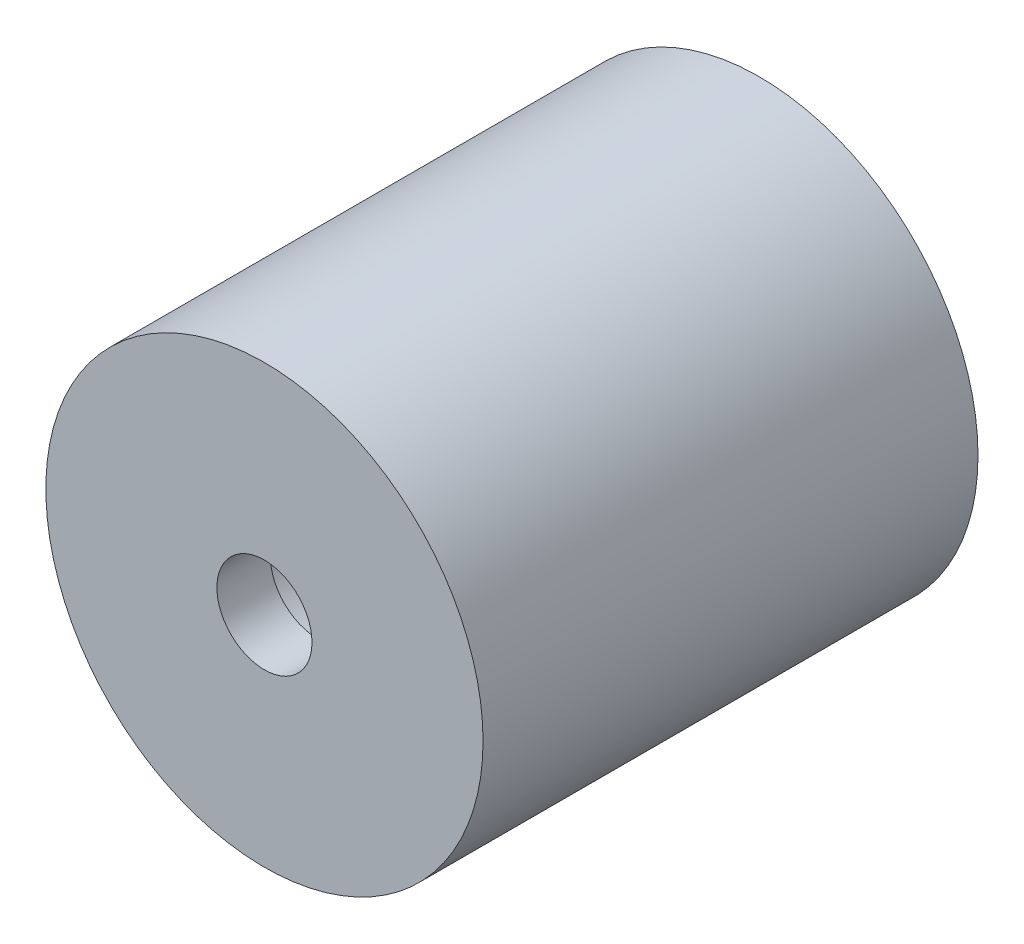
SolidWorks part; units mm, degrees
ref_plane "Front Plane" through (0, 0, 0) normal (0, 0, 1) x (1, 0, 0)
ref_plane "Top Plane" through (0, 0, 0) normal (0, 1, 0) x (1, 0, 0)
ref_plane "Right Plane" through (0, 0, 0) normal (1, 0, 0) x (0, 0, -1)
sketch "Sketch1" plane through (0, 0, 0) normal (0, 0, 1) x (1, 0, 0)
  circle A0 centre (0, 0) radius 3.175
  circle A1 centre (0, 0) radius 8.175
  circle A2 centre (0, 0) radius 1.778
  dimension "D1" = 6.35
  dimension "D3" = 3.556
  dimension "D2" = 5
extrude "Boss-Extrude1" add sketch "Sketch1" along normal blind 2 contours A0 A2 | A1 A0 region at (-3.0852, 0, 0) region at (-7.9438, 0, 0)
extrude "Boss-Extrude2" add sketch "Sketch1<3>" against normal blind 16.51 contours A1 A0 region at (-7.9438, 0, 0)
sketch "Sketch1<3>" plane through (0, 0, 0) normal (0, 0, 1) x (1, 0, 0) same geometry as "Sketch1"
